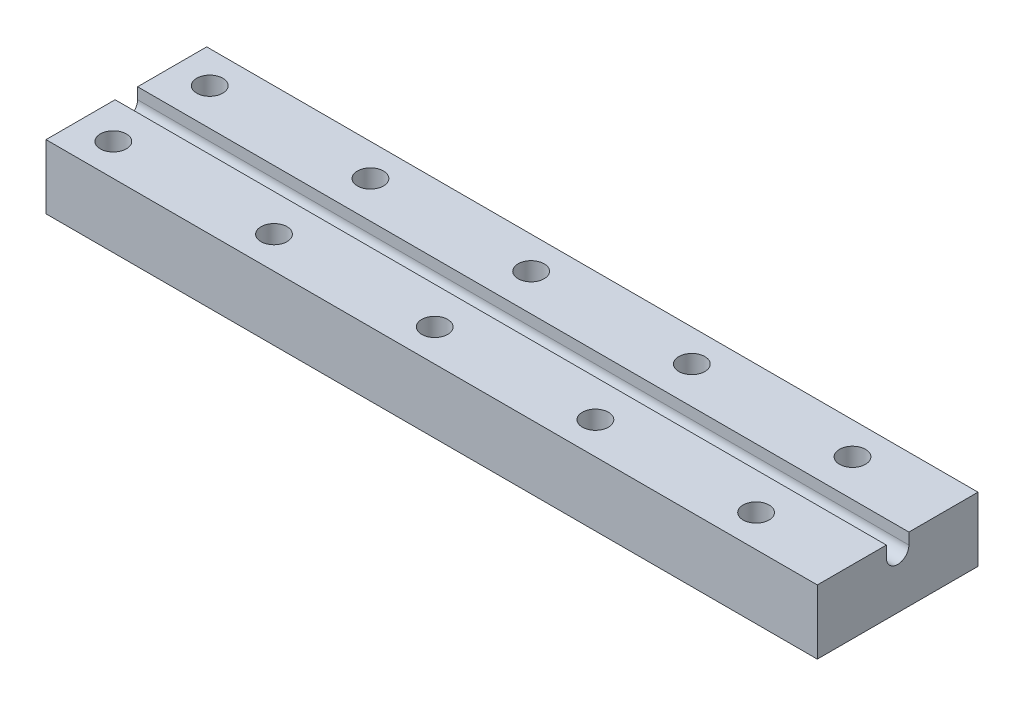
SolidWorks part; units mm, degrees
material "Copper"
ref_plane "Front Plane" through (0, 0, 0) normal (0, 0, 1) x (1, 0, 0)
ref_plane "Top Plane" through (0, 0, 0) normal (0, 1, 0) x (1, 0, 0)
ref_plane "Right Plane" through (0, 0, 0) normal (1, 0, 0) x (0, 0, -1)
sketch "Sketch1" plane through (0, 0, 0) normal (0, 1, 0) x (1, 0, 0)
  line L1 (0, 0) -> (240, 0)
  line L2 (0, 0) -> (0, 50)
  line L3 (0, 50) -> (240, 50)
  line L4 (240, 0) -> (240, 50)
  dimension "D1" = 240
  dimension "D2" = 50
extrude "Boss-Extrude1" add sketch "Sketch1" along normal blind 20
sketch "Sketch2" plane through (0, 0, 0) normal (-1, 0, 0) x (0, 0, 1)
  line L0 (-50, 20) -> (0, 20)
  line L1 (-25, 20) -> (-25, 0)
  line L2 (-50, 0) -> (0, 0) construction
  line L3 (-28.5, 16.5) -> (-28.5, 20)
  line L4 (-21.5, 16.5) -> (-21.5, 20)
  circle A0 centre (-25, 16.5) radius 3.5
  dimension "D1" = 7
extrude "Cut-Extrude1" cut sketch "Sketch2" against normal blind 254 and the other way blind 30 contours A0 L0 L3 | A0 L1 | A0 L4 L0 | L1 A0 region at (0, 19.2182, -27.7182) region at (0, 16.5, -23.5146) region at (0, 19.2182, -22.2818) region at (0, 16.5, -26.4854)
ref_plane "Plane1" through (0, 0, 0) normal (0, -1, 0) x (-1, 0, 0)
sketch "Sketch3" plane through (0, 0, 0) normal (0, -1, 0) x (1, 0, 0)
  line L0 (240, 0) -> (0, 0)
  line L1 (0, -10) -> (10.95, -10)
  line L2 (0, -25) -> (9.8353, -25)
  line L3 (240, 0) -> (120, 0)
  line L4 (120, 0) -> (0, 0)
  line L5 (0, -50) -> (0, 0) construction
  line L6 (120, 0) -> (0, 0)
  line L7 (10.95, -10) -> (10.95, 0)
  circle A0 centre (10.95, -10) radius 4.05
  circle A1 centre (10.95, -40) radius 4.05
  circle A2 centre (60.95, -10) radius 4.05
  circle A3 centre (60.95, -40) radius 4.05
  circle A4 centre (110.95, -10) radius 4.05
  circle A5 centre (110.95, -40) radius 4.05
  circle A6 centre (160.95, -10) radius 4.05
  circle A7 centre (160.95, -40) radius 4.05
  circle A8 centre (210.95, -10) radius 4.05
  circle A9 centre (210.95, -40) radius 4.05
  point P23 (0, 0)
  dimension "D1" = 10.95
  dimension "D2" = 10
  dimension "D3" = 8.1
extrude "Cut-Extrude2" cut sketch "Sketch3" against normal blind 67 contours A4 | A4 | A6 | A6 | A7 | A5 | A2 | A3 | A8 | A9 | A1 | A0 region at (110.95, 0, -10) region at (160.95, 0, -10)
